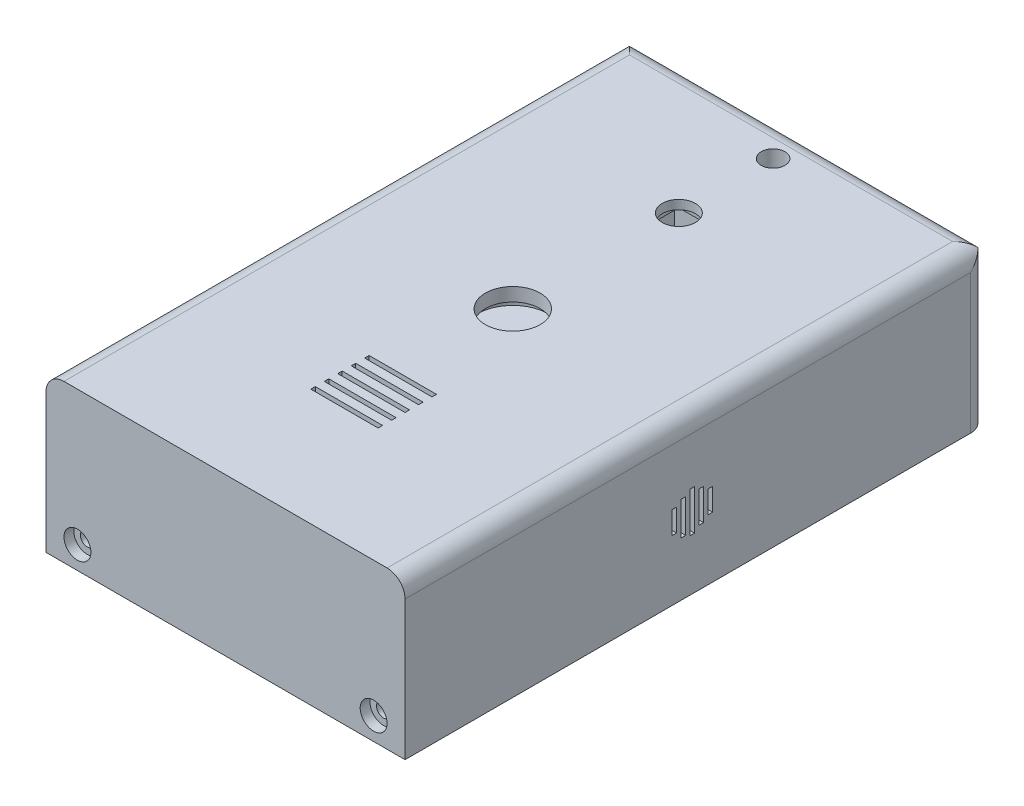
SolidWorks part; units mm, degrees
ref_plane "Front Plane" through (0, 0, 0) normal (0, 0, 1) x (1, 0, 0)
ref_plane "Top Plane" through (0, 0, 0) normal (0, 1, 0) x (1, 0, 0)
ref_plane "Right Plane" through (0, 0, 0) normal (1, 0, 0) x (0, 0, -1)
sketch "Sketch1" plane through (0, 0, 0) normal (0, 1, 0) x (1, 0, 0)
  line L1 (0, 0) -> (80, 0)
  line L2 (0, 0) -> (0, 130)
  line L3 (0, 130) -> (80, 130)
  line L4 (80, 0) -> (80, 130)
  arc A0 (0, 126) -> (4, 130) centre (4, 126) cw
  arc A1 (80, 126) -> (76, 130) centre (76, 126) ccw
  point P5 (4, 126)
  point P6 (76, 126)
  dimension "D7" = 4
  dimension "D8" = 4
  dimension "D1" = 80
  dimension "D2" = 130
  dimension "D3" = 4
  dimension "D4" = 4
  dimension "D5" = 4
  dimension "D6" = 4
extrude "Boss-Extrude1" add sketch "Sketch1" along normal blind 35 contours L4 A1 L3 A0 L2 L1 region at (40, 0, -64.9576)
sketch "Sketch2" plane through (0, 0, 0) normal (-1, 0, 0) x (0, 0, 1)
  line L1 (-126, 35) -> (-130, 35)
  line L2 (-126, 35) -> (-126, 31)
  line L3 (-126, 31) -> (-130, 31)
  line L4 (-130, 35) -> (-130, 31)
  arc A0 (-130, 31) -> (-126, 35) centre (-126, 31) cw
  dimension "D1" = 4
  dimension "D2" = 4
extrude "Cut-Extrude4" cut sketch "Sketch2" against normal up to surface (80 mm away) contours L4 A0 L1 region at (0, 34.1065, -129.1065) up to face at (80, 17.5, -63)
sketch "Sketch3" plane through (0, 0, 0) normal (0, 0, 1) x (1, 0, 0)
  line L0 (0, 35) -> (80, 35) construction
  line L1 (0, 35) -> (0, 0) construction
  line L2 (80, 35) -> (80, 0) construction
  arc A0 (0, 31) -> (4, 35) centre (4, 31) cw
  arc A1 (76, 35) -> (80, 31) centre (76, 31) cw
  point P0 (4, 31)
  point P5 (76, 31)
  line M2 (80, 0) -> (80, 35)
  line M3 (80, 35) -> (0, 35)
  line M4 (0, 35) -> (0, 0)
  dimension "D5" = 4
  dimension "D6" = 4
  dimension "D1" = 4
  dimension "D2" = 4
  dimension "D3" = 4
  dimension "D4" = 4
extrude "Cut-Extrude5" cut sketch "Sketch3" against normal through all contours A0 M4 M3 | A1 M3 M2 region at (0.8935, 34.1065, 0) region at (79.1065, 34.1065, 0)
sketch "Sketch4" plane through (0, 0, 0) normal (0, -1, 0) x (1, 0, 0)
  line L1 (78, -128) -> (2, -128)
  line L2 (78, -128) -> (78, -2)
  line L3 (78, -2) -> (2, -2)
  line L4 (2, -128) -> (2, -2)
  line L6 (0, 0) -> (0, -126) construction
  line L7 (4, -130) -> (76, -130) construction
  dimension "D1" = 2
  dimension "D2" = 2
  dimension "D3" = 2
  dimension "D4" = 2
extrude "Cut-Extrude6" cut sketch "Sketch4" against normal blind 33
sketch "Sketch5" plane through (0, 0, -2) normal (0, 0, -1) x (-1, 0, 0)
  line L1 (-78, 33) -> (-77, 33)
  line L2 (-78, 33) -> (-78, 32)
  line L3 (-78, 32) -> (-77, 32)
  line L4 (-77, 33) -> (-77, 32)
  line L5 (-2, 33) -> (-3, 33)
  line L6 (-2, 33) -> (-2, 32)
  line L7 (-2, 32) -> (-3, 32)
  line L8 (-3, 33) -> (-3, 32)
  dimension "D1" = 1
  dimension "D2" = 1
  dimension "D3" = 1
  dimension "D4" = 1
extrude "Boss-Extrude2" add sketch "Sketch5" along normal up to surface (126 mm away) up to face at (40, 16.5, -128)
sketch "Sketch6" plane through (3, 0, 0) normal (1, 0, 0) x (0, 0, -1)
  line L0 (128, 33) -> (2, 33) construction
  line L1 (128, 32) -> (127, 32)
  line L2 (128, 32) -> (128, 33)
  line L3 (128, 33) -> (127, 33)
  line L4 (127, 32) -> (127, 33)
  dimension "D1" = 1
extrude "Boss-Extrude3" add sketch "Sketch6" along normal up to surface (75 mm away) up to face at (78, 16, -65)
sketch "Sketch9" plane through (0, 33, 0) normal (0, -1, 0) x (-1, 0, 0)
  line L0 (-77, 127) -> (-3, 127) construction
  line L3 (-47.5, 126) -> (-32.5, 126)
  line L4 (-47.5, 126) -> (-47.5, 118)
  line L5 (-47.5, 118) -> (-32.5, 118)
  line L6 (-32.5, 126) -> (-32.5, 118)
  circle A0 centre (-40, 122) radius 2.65
  circle A1 centre (-40, 122) radius 3.65
  dimension "D1" = 5.3
  dimension "D4" = 15
  dimension "D8" = 7.3
  dimension "D2" = 29.5
  dimension "D3" = 1
  dimension "D5" = 7.5
  dimension "D6" = 4
  dimension "D7" = 8
extrude "Boss-Extrude4" add sketch "Sketch9" along normal blind 3 contours L6 L3 L4 L5 A1 region at (40, 33, -125.83)
extrude "Boss-Extrude5" add sketch "Sketch9<7>" along normal blind 2 contours A1 A0 region at (43.5468, 33, -122)
sketch "Sketch9<7>" plane through (0, 33, 0) normal (0, -1, 0) x (-1, 0, 0) same geometry as "Sketch9"
extrude "Cut-Extrude7" cut sketch "Sketch9<8>" against normal up to surface (2 mm away) contours A0 region at (40, 33, -122) up to face at (40, 35, -63)
sketch "Sketch9<8>" plane through (0, 33, 0) normal (0, -1, 0) x (-1, 0, 0) same geometry as "Sketch9"
sketch "Sketch11" plane through (0, 33, 0) normal (0, -1, 0) x (-1, 0, 0)
  line L1 (-44.5, 105.5) -> (-35.5, 105.5)
  line L2 (-44.5, 105.5) -> (-44.5, 96.5)
  line L3 (-44.5, 96.5) -> (-35.5, 96.5)
  line L4 (-35.5, 105.5) -> (-35.5, 96.5)
  line L5 (-52.5, 113) -> (-27.5, 113)
  line L6 (-52.5, 113) -> (-52.5, 89)
  line L7 (-52.5, 89) -> (-27.5, 89)
  line L8 (-27.5, 113) -> (-27.5, 89)
  line L9 (-46.5, 96.5) -> (-46.5, 89)
  line L10 (-33.5, 96.5) -> (-33.5, 89)
  line L11 (-46.5, 96.5) -> (-44.5, 96.5)
  line L12 (-46.5, 96.5) -> (-44.5, 96.5)
  line L13 (-35.5, 96.5) -> (-33.5, 96.5)
  circle A0 centre (-40, 101) radius 3.7
  dimension "D3" = 7.4
  dimension "D1" = 9
  dimension "D2" = 9
  dimension "D4" = 4.5
  dimension "D5" = 4.5
  dimension "D6" = 25
  dimension "D7" = 24
  dimension "D8" = 7.5
  dimension "D9" = 8
  dimension "D10" = 5
  dimension "D11" = 5
  dimension "D12" = 7.5
  dimension "D13" = 2
  dimension "D14" = 7.5
  dimension "D15" = 2
extrude "Boss-Extrude6" add sketch "Sketch11" along normal blind 1.5 contours L4 L13 L10 L7 L8 L5 L6 L9 L11 L2 L1 region at (44.8466, 33, -101)
extrude "Cut-Extrude8" cut sketch "Sketch11<9>" against normal up to surface (2 mm away) contours A0 region at (40, 33, -101) up to face at (40, 35, -119.35)
sketch "Sketch11<9>" plane through (0, 33, 0) normal (0, -1, 0) x (-1, 0, 0) same geometry as "Sketch11"
sketch "Sketch13" plane through (0, 31.5, 0) normal (0, -1, 0) x (-1, 0, 0)
  line L0 (-52.5, 113) -> (-52.5, 89) construction
  line L1 (-52.5, 89) -> (-46.5, 89) construction
  line L2 (-27.5, 113) -> (-27.5, 89) construction
  circle A0 centre (-50.5, 91) radius 1
  circle A1 centre (-50.5, 103.5) radius 1.2912
  circle A2 centre (-29.5, 91) radius 1
  circle A3 centre (-29.5, 103.5) radius 1
  dimension "D3" = 2
  dimension "D5" = 2.5823
  dimension "D8" = 2
  dimension "D10" = 2
  dimension "D1" = 2
  dimension "D2" = 2
  dimension "D4" = 12.5
  dimension "D6" = 2
  dimension "D7" = 21
  dimension "D9" = 2
  dimension "D11" = 2
  dimension "D12" = 12.5
extrude "Boss-Extrude7" add sketch "Sketch13" along normal blind 3
sketch "Sketch14" plane through (0, 33, 0) normal (0, -1, 0) x (-1, 0, 0)
  line L0 (-77, 127) -> (-77, 2) construction
  line L1 (-34.0873, 65.5) -> (-31.1259, 65.5)
  line L2 (-50, 74) -> (-65, 74)
  line L3 (-33.9, 64) -> (-31, 64)
  line L4 (-40, 70.1) -> (-40, 73)
  line L5 (-46.1, 64) -> (-49, 64)
  line L6 (-40, 57.9) -> (-40, 55)
  line L7 (-34.0873, 62.5) -> (-31.1259, 62.5)
  line L8 (-41.5, 58.0873) -> (-41.5, 55.1259)
  line L9 (-38.5, 58.0873) -> (-38.4718, 55.1307)
  line L10 (-45.9127, 65.5) -> (-48.8741, 65.5)
  line L11 (-45.9127, 62.5) -> (-48.8741, 62.5)
  line L12 (-41.5, 69.9127) -> (-41.5, 72.8741)
  line L13 (-38.5, 72.8741) -> (-38.5, 69.9127)
  line L14 (-65, 74) -> (-65, 54)
  line L15 (-50, 74) -> (-30, 74)
  line L16 (-50, 74) -> (-50, 54)
  line L17 (-50, 54) -> (-30, 54)
  line L18 (-30, 74) -> (-30, 54)
  line L19 (-65, 54) -> (-50, 54)
  line L20 (-77, 127) -> (-3, 127) construction
  line L21 (-30, 54) -> (-15, 54)
  line L22 (-15, 54) -> (-15, 74)
  line L23 (-15, 74) -> (-30, 74)
  circle A0 centre (-40, 64) radius 6.1
  circle A1 centre (-40, 64) radius 8
  circle A2 centre (-40, 64) radius 9
  dimension "D1" = 12.2
  dimension "D4" = 16
  dimension "D5" = 18
  dimension "D2" = 37
  dimension "D3" = 63
  dimension "D6" = 1.5
  dimension "D7" = 1.5
  dimension "D8" = 1.5
  dimension "D9" = 1.5
  dimension "D10" = 2.9566
  dimension "D11" = 20
  dimension "D12" = 20
  dimension "D13" = 10
  dimension "D14" = 10
  dimension "D15" = 15
  dimension "D16" = 15
extrude "Cut-Extrude9" cut sketch "Sketch14" against normal blind 2 contours A0 region at (40, 33, -64)
extrude "Boss-Extrude8" add sketch "Sketch14<7>" along normal blind 1 contours L12 A1 L10 A0 | L4 A1 L12 A0 | L13 A1 L4 A0 | L1 A1 L13 A0 | L3 A1 L1 A0 | L7 A1 L3 A0 | L9 A1 L7 A0 | L6 A1 L9 A0 | L8 A1 L6 A0 | L11 A1 L8 A0 | L5 A1 L11 A0 | L10 A1 L5 A0 region at (35.2438, 33, -68.7562) region at (33.0049, 33, -64.7529) region at (33.0049, 33, -63.2471) region at (39.2471, 33, -70.9951) region at (35.24, 33, -59.2467) region at (40.7529, 33, -70.9951) region at (39.2424, 33, -57.0036) region at (44.7562, 33, -68.7562) region at (40.7529, 33, -57.0049) region at (46.9951, 33, -64.7529) region at (44.7562, 33, -59.2438) region at (46.9951, 33, -63.2471)
sketch "Sketch14<7>" plane through (0, 33, 0) normal (0, -1, 0) x (-1, 0, 0) same geometry as "Sketch14"
extrude "Boss-Extrude11" add sketch "Sketch14<11>" along normal blind 3 contours L14 L19 L16 L2 | L18 L15 L16 L17 A2 | L22 L23 L18 L21 | L1 A2 L13 A1 | L13 A2 L4 A1 | L4 A2 L12 A1 | L12 A2 L10 A1 | L10 A2 L5 A1 | L5 A2 L11 A1 | L11 A2 L8 A1 | L8 A2 L6 A1 | L6 A2 L9 A1 | L9 A2 L7 A1 | L7 A2 L3 A1 | L3 A2 L1 A1 region at (34.2694, 33, -69.7306) region at (31.5447, 33, -64.752) region at (31.5447, 33, -63.248) region at (39.248, 33, -72.4553) region at (31.6339, 33, -62.3959) region at (40.752, 33, -72.4553) region at (39.2362, 33, -55.5455) region at (45.7306, 33, -69.7306) region at (40.752, 33, -55.5447) region at (48.4553, 33, -64.752) region at (41.6043, 33, -55.6339) region at (48.4553, 33, -63.248) region at (57.5, 33, -64) region at (40, 33, -73.7172) region at (22.5, 33, -64)
sketch "Sketch14<11>" plane through (0, 33, 0) normal (0, -1, 0) x (-1, 0, 0) same geometry as "Sketch14"
sketch "Sketch23" plane through (65, 0, 0) normal (1, 0, 0) x (0, 0, -1)
  line L1 (74, 33) -> (54, 33)
  line L2 (74, 33) -> (74, 30)
  line L3 (74, 30) -> (54, 30)
  line L4 (54, 33) -> (54, 30)
extrude "Boss-Extrude12" add sketch "Sketch23" along normal up to surface (13 mm away) up to face at (78, 16, -65)
sketch "Sketch24" plane through (15, 0, 0) normal (-1, 0, 0) x (0, 0, 1)
  line L1 (-74, 30) -> (-54, 30)
  line L2 (-74, 30) -> (-74, 33)
  line L3 (-74, 33) -> (-54, 33)
  line L4 (-54, 30) -> (-54, 33)
extrude "Boss-Extrude13" add sketch "Sketch24" along normal up to surface (13 mm away) up to face at (2, 16, -65)
sketch "Sketch25" plane through (0, 33, 0) normal (0, -1, 0) x (1, 0, 0)
  line L1 (78, -128) -> (78, -2) construction
  line L3 (33, -29) -> (48, -29)
  line L4 (33, -26) -> (48, -26)
  line L5 (33, -26) -> (33, -27)
  line L6 (33, -27) -> (48, -27)
  line L7 (48, -26) -> (48, -27)
  line L8 (33, -29) -> (33, -30)
  line L9 (33, -30) -> (48, -30)
  line L10 (48, -29) -> (48, -30)
  line L11 (33, -32) -> (48, -32)
  line L12 (33, -32) -> (33, -33)
  line L13 (33, -33) -> (48, -33)
  line L14 (48, -32) -> (48, -33)
  line L15 (33, -35) -> (48, -35)
  line L16 (33, -35) -> (33, -36)
  line L17 (33, -36) -> (48, -36)
  line L18 (48, -35) -> (48, -36)
  line L19 (33, -38) -> (48, -38)
  line L20 (33, -38) -> (33, -39)
  line L21 (33, -39) -> (48, -39)
  line L22 (48, -38) -> (48, -39)
  line L24 (77, -2) -> (3, -2) construction
  circle A0 centre (40.5, -32) radius 20.25
  circle A1 centre (40.5, -32) radius 21
  dimension "D1" = 40.5
  dimension "D24" = 30
  dimension "D3" = 37.5
  dimension "D4" = 15
  dimension "D5" = 7.5
  dimension "D6" = 5
  dimension "D7" = 1
  dimension "D8" = 15
  dimension "D9" = 1
  dimension "D10" = 15
  dimension "D11" = 1
  dimension "D12" = 15
  dimension "D13" = 1
  dimension "D14" = 15
  dimension "D15" = 1
  dimension "D16" = 2
  dimension "D17" = 2
  dimension "D18" = 2
  dimension "D19" = 0
  dimension "D20" = 0
  dimension "D21" = 0
  dimension "D22" = 0
  dimension "D23" = 2
extrude "Cut-Extrude10" cut sketch "Sketch25" against normal up to surface (2 mm away) contours L22 L19 L20 L21 | L18 L15 L16 L17 | L14 L11 L12 L13 | L7 L4 L5 L6 | L9 L10 L3 L8 region at (40.5, 33, -26.5) region at (40.5, 33, -32.5) region at (40.5, 33, -35.5) region at (40.5, 33, -38.5) up to face at (40, 35, -70.1)
extrude "Boss-Extrude14" add sketch "Sketch25<5>" along normal blind 1 contours A1 A0 region at (20.094, 33, -32)
sketch "Sketch25<5>" plane through (0, 33, 0) normal (0, -1, 0) x (1, 0, 0) same geometry as "Sketch25"
sketch "Sketch27" plane through (2, 0, 0) normal (1, 0, 0) x (0, 0, -1)
  line L0 (2, 0) -> (128, 0) construction
  line L1 (118, 7) -> (48, 7)
  line L2 (118, 7) -> (118, 4)
  line L3 (118, 4) -> (48, 4)
  line L4 (48, 7) -> (48, 4)
  line L6 (128, 32) -> (128, 0) construction
  dimension "D1" = 23
  dimension "D2" = 3
  dimension "D3" = 70
  dimension "D4" = 10
extrude "Boss-Extrude16" add sketch "Sketch27" along normal blind 33 separate body
sketch "Sketch28" plane through (0, 7, 0) normal (0, 1, 0) x (1, 0, 0)
  line L0 (35, 118) -> (35, 48) construction
  line L1 (4, 115) -> (34, 115)
  line L2 (4, 115) -> (4, 50)
  line L3 (4, 50) -> (34, 50)
  line L4 (34, 115) -> (34, 50)
  circle A0 centre (7.5, 111.5) radius 1.2
  circle A1 centre (7.5, 53.5) radius 1.2
  circle A2 centre (30.5, 111.5) radius 1.2
  circle A3 centre (30.5, 53.5) radius 1.2
  dimension "D7" = 2.4
  dimension "D10" = 2.4
  dimension "D13" = 2.4
  dimension "D14" = 2.4
  dimension "D1" = 65
  dimension "D2" = 30
  dimension "D3" = 2
  dimension "D4" = 1
  dimension "D5" = 3.5
  dimension "D6" = 3.5
  dimension "D8" = 3.5
  dimension "D9" = 3.5
  dimension "D11" = 3.5
  dimension "D12" = 3.5
  dimension "D15" = 3.5
  dimension "D16" = 3.5
extrude "Boss-Extrude17" add sketch "Sketch28" along normal blind 8 contours A1 | A3 | A2 | A0 region at (7.5, 7, -111.5) region at (7.5, 7, -53.5) region at (30.5, 7, -111.5) region at (30.5, 7, -53.5)
sketch "Sketch29" plane through (0, 0, -2) normal (0, 0, -1) x (-1, 0, 0)
  line L1 (-2, 0) -> (-12, 0)
  line L2 (-2, 0) -> (-2, 10)
  line L3 (-2, 10) -> (-12, 10)
  line L4 (-12, 0) -> (-12, 10)
  dimension "D1" = 10
  dimension "D2" = 10
extrude "Boss-Extrude18" add sketch "Sketch29" along normal blind 10
sketch "Sketch30" plane through (2, 0, 0) normal (1, 0, 0) x (0, 0, -1)
  line L0 (54, 32) -> (2, 32) construction
  line L1 (41, 10) -> (21, 10)
  line L2 (41, 10) -> (41, 7)
  line L3 (41, 7) -> (21, 7)
  line L4 (21, 10) -> (21, 7)
  line L5 (2, 32) -> (2, 10) construction
  dimension "D1" = 3
  dimension "D2" = 22
  dimension "D3" = 19
  dimension "D4" = 20
sketch "Sketch31" plane through (0, 0, -12) normal (0, 0, -1) x (-1, 0, 0)
  line L2 (-12, 0) -> (-2, 0) construction
  line L3 (-8.7321, 8) -> (-10.4641, 5)
  line L4 (-10.4641, 5) -> (-8.7321, 2)
  line L5 (-8.7321, 2) -> (-5.2679, 2)
  line L6 (-5.2679, 2) -> (-3.5359, 5)
  line L7 (-3.5359, 5) -> (-5.2679, 8)
  line L8 (-5.2679, 8) -> (-8.7321, 8)
  line L9 (-12, 10) -> (-12, 0) construction
  circle A0 centre (-7, 5) radius 3 construction
  dimension "D3" = 5
  dimension "D1" = 6
  dimension "D2" = 6
  dimension "D4" = 5
extrude "Boss-Extrude19" add sketch "Sketch30" along normal up to surface (76 mm away) up to face at (78, 23.5, -64.5)
extrude "Cut-Extrude11" cut sketch "Sketch31" against normal blind 3
sketch "Sketch34" plane through (0, 0, -9) normal (0, 0, -1) x (-1, 0, 0)
  line L1 (-5.2679, 8) -> (-8.7321, 8) construction
  line L2 (-3.5359, 5) -> (-5.2679, 8) construction
  circle A0 centre (-7, 5) radius 1.55
  dimension "D3" = 3.1
  dimension "D1" = 3
  dimension "D2" = 3
extrude "Cut-Extrude12" cut sketch "Sketch34" against normal up to surface (9 mm away) up to face at (40, 22.2761, 0)
sketch "Sketch35" plane through (0, 0, -2) normal (0, 0, -1) x (-1, 0, 0)
  line L1 (-78, 0) -> (-68, 0)
  line L2 (-78, 0) -> (-78, 10)
  line L3 (-78, 10) -> (-68, 10)
  line L4 (-68, 0) -> (-68, 10)
  dimension "D1" = 10
  dimension "D2" = 10
extrude "Boss-Extrude21" add sketch "Sketch35" along normal blind 10
sketch "Sketch36" plane through (0, 0, -12) normal (0, 0, -1) x (-1, 0, 0)
  line L0 (-78, 0) -> (-68, 0) construction
  line L1 (-71.2679, 2) -> (-69.5359, 5)
  line L2 (-69.5359, 5) -> (-71.2679, 8)
  line L3 (-71.2679, 8) -> (-74.7321, 8)
  line L4 (-74.7321, 8) -> (-76.4641, 5)
  line L5 (-76.4641, 5) -> (-74.7321, 2)
  line L6 (-74.7321, 2) -> (-71.2679, 2)
  line L7 (-68, 0) -> (-68, 10) construction
  line L8 (-3.5359, 5) -> (-5.2679, 8) construction
  circle A0 centre (-73, 5) radius 3 construction
  dimension "D1" = 6
  dimension "D2" = 5
  dimension "D3" = 5
  dimension "D4" = 3
extrude "Cut-Extrude13" cut sketch "Sketch36" against normal blind 3
sketch "Sketch37" plane through (0, 0, -9) normal (0, 0, -1) x (-1, 0, 0)
  line L0 (-71.2679, 8) -> (-74.7321, 8) construction
  line L1 (-69.5359, 5) -> (-71.2679, 8) construction
  circle A0 centre (-73, 5) radius 1.55
  point P4 (-73, 8)
  dimension "D1" = 3.1
  dimension "D2" = 3
  dimension "D3" = 3
extrude "Cut-Extrude14" cut sketch "Sketch37" against normal up to surface (9 mm away) up to face at (5.45, 5, 0)
sketch "Sketch38" plane through (0, 0, 0) normal (0, 0, 1) x (1, 0, 0)
  line L0 (80, 31) -> (80, 0) construction
  line L1 (0, 0) -> (80, 0) construction
  circle A0 centre (73, 5) radius 3
  dimension "D3" = 6
  dimension "D1" = 7
  dimension "D2" = 5
extrude "Cut-Extrude15" cut sketch "Sketch38" against normal blind 2.2
sketch "Sketch39" plane through (0, 0, 0) normal (0, 0, 1) x (1, 0, 0)
  line L0 (0, 0) -> (80, 0) construction
  line L1 (0, 31) -> (0, 0) construction
  circle A0 centre (7, 5) radius 3
  dimension "D1" = 6
  dimension "D2" = 5
  dimension "D3" = 7
extrude "Cut-Extrude16" cut sketch "Sketch39" against normal blind 2.2
sketch "Sketch40" plane through (78, 0, 0) normal (-1, 0, 0) x (0, 0, 1)
  line L0 (-54, 32) -> (-2, 32) construction
  line L1 (-53, 32) -> (-34, 32)
  line L2 (-53, 32) -> (-53, 13)
  line L3 (-53, 13) -> (-34, 13)
  line L4 (-34, 32) -> (-34, 13)
  circle A0 centre (-37, 16) radius 1
  circle A1 centre (-37, 29) radius 1
  dimension "D5" = 2
  dimension "D7" = 2
  dimension "D1" = 19
  dimension "D2" = 19
  dimension "D3" = 1
  dimension "D4" = 3
  dimension "D6" = 3
  dimension "D8" = 3
  dimension "D9" = 3
extrude "Boss-Extrude22" add sketch "Sketch40" along normal blind 7 contours A0 | A1 region at (78, 16, -37) region at (78, 29, -37)
sketch "Sketch41" plane through (0, 7, 0) normal (0, -1, 0) x (1, 0, 0)
  line L0 (78, -21) -> (78, -41) construction
  line L3 (23, -41) -> (23, -21)
  line L4 (78, -41) -> (2, -41) construction
  line L5 (78, -21) -> (2, -21) construction
  line L6 (57, -41) -> (57, -21)
  line L7 (30.8, -41) -> (30.8, -21)
  line L8 (49.2, -41) -> (49.2, -21)
  circle A0 centre (40, -31) radius 9.2
  point P12 (30.8, -31)
  point P13 (49.2, -31)
  line M4 (78, -21) -> (2, -21)
  line M6 (2, -41) -> (78, -41)
  dimension "D1" = 18.4
  dimension "D2" = 38
  dimension "D3" = 17
  dimension "D4" = 17
  dimension "D5" = 10
extrude "Boss-Extrude23" add sketch "Sketch41" along normal blind 1 and the other way blind 10 contours L8 L6 M6 M4 | L7 L3 M6 M4 region at (26.9, 7, -31) region at (53.1, 7, -31)
sketch "Sketch42" plane through (0, 0, -21) normal (0, 0, 1) x (1, 0, 0)
  line L0 (49.2, 7) -> (30.8, 7) construction
  line L1 (44.2, 7) -> (35.8, 7)
  line L2 (44.2, 7) -> (44.2, 10)
  line L3 (44.2, 10) -> (35.8, 10)
  line L4 (35.8, 7) -> (35.8, 10)
  line L5 (49.2, 10) -> (30.8, 10) construction
  dimension "D1" = 5
  dimension "D2" = 5
extrude "Boss-Extrude24" add sketch "Sketch42" along normal up to surface (19 mm away) up to face at (40, 19.5, -2)
sketch "Sketch45" plane through (78, 0, 0) normal (-1, 0, 0) x (0, 0, 1)
  line L0 (-54, 32) -> (-2, 32) construction
  line L1 (-57, 23) -> (-78, 23)
  line L2 (-57, 23) -> (-57, 9)
  line L3 (-57, 9) -> (-78, 9)
  line L4 (-78, 23) -> (-78, 9)
  line L5 (-128, 0) -> (-12, 0) construction
  line L9 (-2, 32) -> (-2, 10) construction
  dimension "D1" = 14
  dimension "D2" = 21
  dimension "D3" = 9
  dimension "D4" = 55
extrude "Boss-Extrude25" add sketch "Sketch45" along normal blind 5
sketch "Sketch46" plane through (73, 0, 0) normal (-1, 0, 0) x (0, 0, 1)
  line L0 (-57, 9) -> (-57, 23) construction
  line L1 (-78, 9) -> (-57, 9) construction
  line L2 (-57, 23) -> (-78, 23) construction
  line L3 (-59.5, 18.5) -> (-60.5, 18.5)
  line L4 (-59.5, 18.5) -> (-59.5, 13.5)
  line L5 (-59.5, 13.5) -> (-60.5, 13.5)
  line L6 (-60.5, 18.5) -> (-60.5, 13.5)
  line L7 (-61.5, 19.5) -> (-62.5, 19.5)
  line L8 (-61.5, 19.5) -> (-61.5, 12.0411)
  line L9 (-61.5, 12.0411) -> (-62.5, 12.0411)
  line L10 (-62.5, 19.5) -> (-62.5, 12.0411)
  line L11 (-63.5, 20.4721) -> (-64.5, 20.4721)
  line L12 (-63.5, 20.4721) -> (-63.5, 11.4721)
  line L13 (-63.5, 11.4721) -> (-64.5, 11.4721)
  line L14 (-64.5, 20.4721) -> (-64.5, 11.4721)
  line L15 (-65.5, 19.5) -> (-66.5, 19.5)
  line L16 (-65.5, 19.5) -> (-65.5, 12.5)
  line L17 (-65.5, 12.5) -> (-66.5, 12.5)
  line L18 (-66.5, 19.5) -> (-66.5, 12.5)
  line L19 (-68.5, 18.5) -> (-67.5, 18.5)
  line L20 (-68.5, 18.5) -> (-68.5, 13.5)
  line L21 (-68.5, 13.5) -> (-67.5, 13.5)
  line L22 (-67.5, 18.5) -> (-67.5, 13.5)
  circle A0 centre (-59, 11) radius 1
  circle A1 centre (-59, 21) radius 1
  circle A2 centre (-64, 16) radius 5.15
  dimension "D5" = 2
  dimension "D6" = 2
  dimension "D28" = 10.3
  dimension "D1" = 2
  dimension "D2" = 2
  dimension "D3" = 2
  dimension "D4" = 2
  dimension "D7" = 1
  dimension "D8" = 5
  dimension "D9" = 3.5
  dimension "D10" = 2.5
  dimension "D11" = 1
  dimension "D12" = 7.4589
  dimension "D13" = 3.5
  dimension "D14" = 9
  dimension "D15" = 4.5
  dimension "D16" = 0.5
  dimension "D17" = 1
  dimension "D18" = 1
  dimension "D19" = 7
  dimension "D20" = 3.5
  dimension "D21" = 2.5
  dimension "D22" = 1
  dimension "D23" = 3.5
  dimension "D24" = 2.5
  dimension "D25" = 2.5
  dimension "D26" = 7
  dimension "D27" = 7
  dimension "D29" = 2.5
extrude "Cut-Extrude17" cut sketch "Sketch46" against normal up to surface (7 mm away) contours L22 L19 L20 L21 | L15 L18 L17 L16 | L11 L14 L13 L12 | L7 L10 L9 L8 | L3 L6 L5 L4 region at (73, 16, -60) region at (73, 15.7705, -62) region at (73, 15.9721, -64) region at (73, 16, -66) region at (73, 16, -68) up to face at (80, 15.5, -63)
extrude "Cut-Extrude19" cut sketch "Sketch46<5>" against normal blind 6 contours A2 L19 L22 L21 L20 L6 L3 L4 L5 L10 L7 L8 L9 L14 L11 L12 L13 L18 L15 L16 L17 region at (73, 16, -69.0043)
sketch "Sketch46<5>" plane through (73, 0, 0) normal (-1, 0, 0) x (0, 0, 1) same geometry as "Sketch46"
extrude "Boss-Extrude26" add sketch "Sketch46<6>" along normal blind 6 contours A0 | A1 region at (73, 11, -59) region at (73, 21, -59)
sketch "Sketch46<6>" plane through (73, 0, 0) normal (-1, 0, 0) x (0, 0, 1) same geometry as "Sketch46"
sketch "Sketch47" plane through (78, 0, 0) normal (-1, 0, 0) x (0, 0, 1)
  line L0 (-128, 32) -> (-74, 32) construction
  line L1 (-118, 10) -> (-93, 10)
  line L2 (-118, 10) -> (-118, 25)
  line L3 (-118, 25) -> (-93, 25)
  line L4 (-93, 10) -> (-93, 25)
  line L6 (-94, 11) -> (-117, 11)
  line L7 (-94, 11) -> (-94, 24)
  line L8 (-94, 24) -> (-117, 24)
  line L9 (-117, 11) -> (-117, 24)
  dimension "D1" = 7
  dimension "D2" = 15
  dimension "D3" = 25
  dimension "D4" = 15
  dimension "D5" = 1
  dimension "D6" = 1
  dimension "D7" = 1
  dimension "D8" = 1
extrude "Boss-Extrude27" add sketch "Sketch47" along normal blind 10
sketch "Sketch48" plane through (12, 0, 0) normal (1, 0, 0) x (0, 0, -1)
  line L0 (12, 10) -> (12, 0) construction
  line L1 (12, 2) -> (2, 2)
  line L2 (12, 2) -> (12, 10)
  line L3 (12, 10) -> (2, 10)
  line L4 (2, 2) -> (2, 10)
  dimension "D1" = 8
extrude "Boss-Extrude28" add sketch "Sketch48" along normal blind 10
sketch "Sketch49" plane through (68, 0, 0) normal (-1, 0, 0) x (0, 0, 1)
  line L0 (-2, 0) -> (-2, 10) construction
  line L1 (-12, 10) -> (-2, 10)
  line L2 (-12, 10) -> (-12, 2)
  line L3 (-12, 2) -> (-2, 2)
  line L4 (-2, 10) -> (-2, 2)
  dimension "D1" = 8
extrude "Boss-Extrude29" add sketch "Sketch49" along normal blind 10
sketch "Sketch50" plane through (0, 2, 0) normal (0, -1, 0) x (1, 0, 0)
  line L0 (58, -12) -> (68, -12) construction
  line L1 (58, -12) -> (58, -2) construction
  circle A0 centre (63, -7) radius 1.15
  dimension "D3" = 2.3
  dimension "D1" = 5
  dimension "D2" = 5
extrude "Cut-Extrude20" cut sketch "Sketch50" against normal blind 4
sketch "Sketch51" plane through (0, 2, 0) normal (0, -1, 0) x (1, 0, 0)
  line L0 (22, -2) -> (22, -12) construction
  line L1 (22, -12) -> (12, -12) construction
  line L2 (35, -118) -> (2, -118) construction
  line L3 (2, -20) -> (2, -123) construction
  circle A0 centre (17, -7) radius 1.15
  point P2 (22, -7)
  point P5 (17, -12)
  dimension "D3" = 2.3
  dimension "D1" = 5
  dimension "D2" = 5
extrude "Cut-Extrude21" cut sketch "Sketch51" against normal blind 4
sketch "Sketch52" plane through (78, 0, 0) normal (-1, 0, 0) x (0, 0, 1)
  line L1 (-128, 0) -> (-123, 0)
  line L2 (-128, 0) -> (-128, 10)
  line L3 (-128, 10) -> (-123, 10)
  line L4 (-123, 0) -> (-123, 10)
  dimension "D1" = 5
  dimension "D2" = 10
extrude "Boss-Extrude30" add sketch "Sketch52" along normal blind 5
sketch "Sketch53" plane through (0, 0, 0) normal (0, -1, 0) x (-1, 0, 0)
  line L0 (-73, 123) -> (-78, 123) construction
  line L1 (-73, 128) -> (-73, 123) construction
  circle A0 centre (-75.5, 125.5) radius 1.15
  dimension "D3" = 2.3
  dimension "D1" = 2.5
  dimension "D2" = 2.5
extrude "Cut-Extrude22" cut sketch "Sketch53" against normal blind 4
sketch "Sketch54" plane through (73, 0, 0) normal (-1, 0, 0) x (0, 0, 1)
  line L0 (-123, 0) -> (-123, 10) construction
  line L1 (-128, 2) -> (-123, 2)
  line L2 (-128, 2) -> (-128, 10)
  line L3 (-128, 10) -> (-123, 10)
  line L4 (-123, 2) -> (-123, 10)
  dimension "D1" = 0
  dimension "D2" = 0
  dimension "D3" = 5
  dimension "D4" = 8
extrude "Boss-Extrude31" add sketch "Sketch54" along normal blind 5
sketch "Sketch55" plane through (0, 2, 0) normal (0, -1, 0) x (1, 0, 0)
  line L0 (68, -123) -> (73, -123) construction
  line L1 (68, -128) -> (68, -123) construction
  circle A0 centre (70.5, -125.5) radius 1.15
  dimension "D3" = 2.3
  dimension "D1" = 2.5
  dimension "D2" = 2.5
extrude "Cut-Extrude23" cut sketch "Sketch55" against normal blind 4
sketch "Sketch56" plane through (2, 0, 0) normal (1, 0, 0) x (0, 0, -1)
  line L1 (128, 0) -> (123, 0)
  line L2 (128, 0) -> (128, 10)
  line L3 (128, 10) -> (123, 10)
  line L4 (123, 0) -> (123, 10)
  dimension "D1" = 0
  dimension "D2" = 0
  dimension "D3" = 5
  dimension "D4" = 10
extrude "Boss-Extrude32" add sketch "Sketch56" along normal blind 5
sketch "Sketch57" plane through (0, 0, 0) normal (0, -1, 0) x (-1, 0, 0)
  line L0 (-7, 123) -> (-2, 123) construction
  line L1 (-7, 123) -> (-7, 128) construction
  circle A0 centre (-4.5, 125.5) radius 1.15
  point P4 (-7, 125.5)
  dimension "D2" = 2.5
  dimension "D3" = 2.3
  dimension "D1" = 2.5
extrude "Cut-Extrude24" cut sketch "Sketch57" against normal blind 4
sketch "Sketch58" plane through (7, 0, 0) normal (1, 0, 0) x (0, 0, -1)
  line L0 (128, 10) -> (123, 10) construction
  line L1 (123, 2) -> (128, 2)
  line L2 (123, 2) -> (123, 10)
  line L3 (123, 10) -> (128, 10)
  line L4 (128, 2) -> (128, 10)
  dimension "D1" = 0
  dimension "D2" = 0
  dimension "D3" = 5
  dimension "D4" = 8
extrude "Boss-Extrude33" add sketch "Sketch58" along normal blind 5
sketch "Sketch59" plane through (0, 2, 0) normal (0, -1, 0) x (-1, 0, 0)
  line L0 (-12, 123) -> (-12, 128) construction
  line L1 (-12, 123) -> (-7, 123) construction
  circle A0 centre (-9.5, 125.5) radius 1.15
  dimension "D1" = 2.3
  dimension "D2" = 2.5
  dimension "D3" = 2.5
extrude "Cut-Extrude25" cut sketch "Sketch59" against normal blind 4
sketch "Sketch60" plane through (78, 0, 0) normal (-1, 0, 0) x (0, 0, 1)
  line L0 (-123, 0) -> (-12, 0) construction
  line L1 (-20, 0) -> (-18, 0)
  line L2 (-20, 0) -> (-20, 10)
  line L3 (-20, 10) -> (-18, 10)
  line L4 (-18, 0) -> (-18, 10)
  dimension "D1" = 6
  dimension "D2" = 2
  dimension "D3" = 10
extrude "Boss-Extrude34" add sketch "Sketch60" along normal blind 10
sketch "Sketch61" plane through (0, 0, -20) normal (0, 0, -1) x (-1, 0, 0)
  line L0 (-68, 0) -> (-78, 0) construction
  line L1 (-68, 10) -> (-68, 0) construction
  circle A0 centre (-73, 5) radius 1.55
  point P4 (-68, 5)
  dimension "D1" = 3.1
  dimension "D2" = 5
  dimension "D3" = 5
extrude "Cut-Extrude26" cut sketch "Sketch61" against normal up to surface (2 mm away) up to face at (73, 5, -18)
sketch "Sketch62" plane through (2, 0, 0) normal (1, 0, 0) x (0, 0, -1)
  line L0 (12, 0) -> (123, 0) construction
  line L1 (20, 0) -> (18, 0)
  line L2 (20, 0) -> (20, 10)
  line L3 (20, 10) -> (18, 10)
  line L4 (18, 0) -> (18, 10)
  dimension "D1" = 2
  dimension "D2" = 10
  dimension "D3" = 0
  dimension "D4" = 6
extrude "Boss-Extrude35" add sketch "Sketch62" along normal blind 10
sketch "Sketch63" plane through (0, 0, -20) normal (0, 0, -1) x (-1, 0, 0)
  line L0 (-12, 0) -> (-2, 0) construction
  line L1 (-2, 0) -> (-2, 10) construction
  circle A0 centre (-7, 5) radius 1.55
  dimension "D3" = 3.1
  dimension "D1" = 5
  dimension "D2" = 5
extrude "Cut-Extrude27" cut sketch "Sketch63" against normal up to surface (2 mm away) up to face at (7, 5, -18)
ref_plane "Plane21" through (80, 0, 0) normal (0, 0, -1) x (-1, 0, 0)
sketch "Sketch64" plane through (80, 0, 0) normal (0, 0, -1) x (-1, 0, 0)
